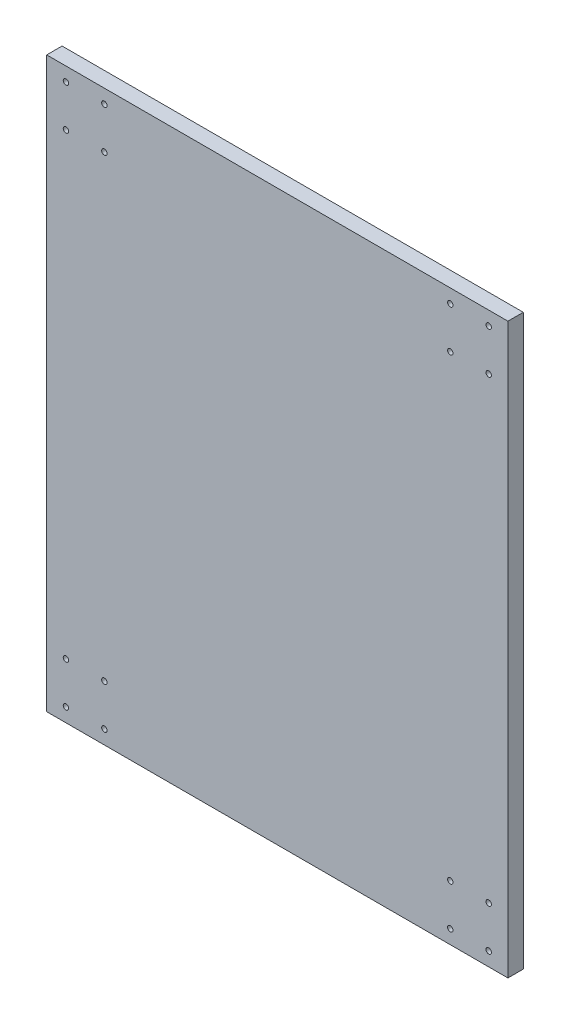
SolidWorks part; units mm, degrees
material "АД1 ГОСТ 4784-97"
ref_plane "Спереди" through (0, 0, 0) normal (0, 0, 1) x (1, 0, 0)
ref_plane "Сверху" through (0, 0, 0) normal (0, 1, 0) x (1, 0, 0)
ref_plane "Справа" through (0, 0, 0) normal (1, 0, 0) x (0, 0, -1)
ref_axis "ОсьX" through (-88.99, 0, 0) along (1, 0, 0)
ref_axis "ОсьZ" through (0, 55, 0) along (0, -1, 0)
ref_axis "ОсьY" through (0, 0, -88.99) along (0, 0, 1)
sketch "Эскиз1" plane through (0, 0, 0) normal (0, 0, 1) x (1, 0, 0)
  line L0 (-250, 300.7732) -> (-250, 212.6152) construction
  line L1 (-300, 370) -> (300, 370)
  line L2 (-300, 370) -> (-300, -370)
  line L3 (-300, -370) -> (300, -370)
  line L4 (300, 370) -> (300, -370)
  line L5 (0, 65.4162) -> (0, -65.4075) construction
  line L6 (-300, 370) -> (-300, -370)
  line L7 (300, 370) -> (300, -370)
  line L8 (-159.2536, 0) -> (189.9089, 0) construction
  circle A0 centre (-275, 352) radius 3.5
  circle A1 centre (-275, 298) radius 3.5
  circle A2 centre (-225, 298) radius 3.5
  circle A3 centre (-225, 352) radius 3.5
  circle A4 centre (225, 352) radius 3.5
  circle A5 centre (225, 298) radius 3.5
  circle A6 centre (275, 298) radius 3.5
  circle A7 centre (275, 352) radius 3.5
  circle A8 centre (-275, -298) radius 3.5
  circle A9 centre (-275, -352) radius 3.5
  circle A10 centre (-225, -352) radius 3.5
  circle A11 centre (-225, -298) radius 3.5
  circle A12 centre (225, -298) radius 3.5
  circle A13 centre (225, -352) radius 3.5
  circle A14 centre (275, -352) radius 3.5
  circle A15 centre (275, -298) radius 3.5
  point P4 (0, 370)
  point P6 (-300, 0)
  dimension "D3" = 7
  dimension "D4" = 54
  dimension "D5" = 50
  dimension "D1" = 600
  dimension "D2" = 740
  dimension "D6" = 500
  dimension "D7" = 650
extrude "Бобышка-Вытянуть1" add sketch "Эскиз1" along normal blind 20 contours L4 L1 L2 L3 A15 A14 A12 A11 A10 A8 A6 A5 A4 A2 A1 A0 A3 A7 A9 A13 region at (0, 0, 0)
